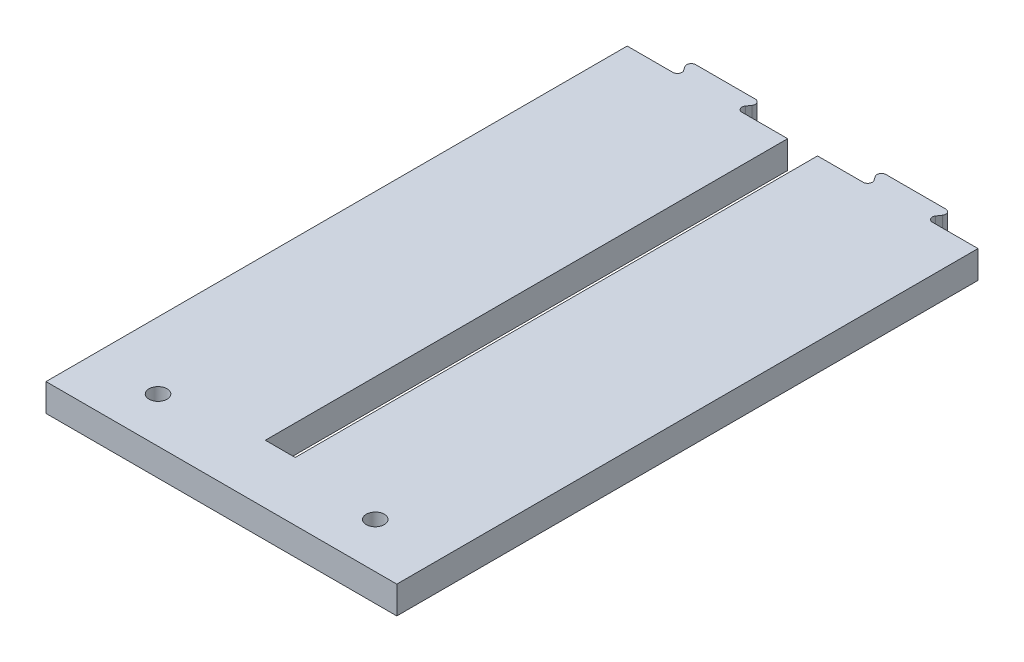
SolidWorks part; units mm, degrees
ref_plane "Front Plane" through (0, 0, 0) normal (0, 0, 1) x (1, 0, 0)
ref_plane "Top Plane" through (0, 0, 0) normal (0, 1, 0) x (1, 0, 0)
ref_plane "Right Plane" through (0, 0, 0) normal (1, 0, 0) x (0, 0, -1)
sketch "Sketch1" plane through (0, 0, 0) normal (0, 1, 0) x (1, 0, 0)
  line L1 (-19.375, 0) -> (19.375, 0)
  line L2 (-19.375, 0) -> (-19.375, 72.5)
  line L3 (-19.375, 72.5) -> (19.375, 72.5)
  line L4 (19.375, 0) -> (19.375, 72.5)
  point P5 (0, 0)
  dimension "D1" = 38.75
  dimension "D2" = 72.5
extrude "Boss-Extrude1" add sketch "Sketch1" along normal blind 3.05 contours L2 | L1 L4 L3 L2 | L4 region at (0, 0, -36.25)
sketch "Sketch4" plane through (0, 3.05, 0) normal (0, 1, 0) x (1, 0, 0)
  line L0 (-19.375, 72.5) -> (19.375, 72.5) construction
  line L2 (-19.375, 0) -> (19.375, 0) construction
  line L3 (1.65, 70.5) -> (-1.65, 70.5)
  line L4 (-1.65, 70.5) -> (-1.65, 69.5)
  line L5 (-1.65, 69.5) -> (1.65, 69.5)
  line L6 (1.65, 69.5) -> (1.65, 70.5)
  line L7 (0, 0) -> (0, 72.5) construction
  line L9 (1.65, 68.3) -> (-1.65, 68.3)
  line L10 (-1.65, 68.3) -> (-1.65, 6.5)
  line L11 (-1.65, 6.5) -> (1.65, 6.5)
  line L12 (1.65, 6.5) -> (1.65, 68.3)
  point P6 (0, 6.5)
  point P10 (0, 70.5)
  point P22 (0, 68.3)
  dimension "D1" = 2
  dimension "D2" = 1
  dimension "D3" = 1.2
  dimension "D4" = 3.3
  dimension "D7" = 6.5
extrude "Cut-Extrude1" cut sketch "Sketch4" against normal through all contours L5 L7 L3 L4 | L11 L7 L9 L10 | L7 L11 L12 L9 | L7 L5 L6 L3 | L6 L3 L4 L5 region at (0.825, 3.05, -70) region at (0.825, 3.05, -37.4) region at (-0.825, 3.05, -37.4) region at (-0.825, 3.05, -70)
sketch "Sketch7" plane through (0, 3.05, 0) normal (0, 1, 0) x (1, 0, 0)
  line L0 (0, 0) -> (-12, 0)
  line L1 (-19.375, 0) -> (19.375, 0) construction
  line L2 (-12, 0) -> (-12, 5)
  line L4 (0, 0) -> (0, 70) construction
  circle A0 centre (-12, 5) radius 1
  circle A2 centre (12, 5) radius 1
  dimension "D3" = 2
  dimension "D1" = 12
  dimension "D2" = 5
extrude "Cut-Extrude4" cut sketch "Sketch7" against normal through all contours A0 L2 | L2 A0 | A2 region at (-11.3129, 3.05, -4.3129)
sketch "Sketch8" plane through (0, 3.05, 0) normal (0, 1, 0) x (1, 0, 0)
  line L0 (19.375, 0) -> (19.375, 72.5) construction
  line L1 (-19.375, 72.5) -> (19.375, 72.5)
  line L2 (-19.375, 72.5) -> (-19.375, 64.2)
  line L3 (-19.375, 64.2) -> (19.375, 64.2)
  line L4 (19.375, 72.5) -> (19.375, 64.2)
  dimension "D1" = 8.3
extrude "Cut-Extrude5" cut sketch "Sketch8" against normal through all
sketch "Sketch9" plane through (0, 3.05, 0) normal (0, 1, 0) x (1, 0, 0)
  line L0 (-19.375, 64.2) -> (19.375, 64.2) construction
  line L1 (-19.375, 64.2) -> (-19.375, 66.2) construction
  line L2 (19.375, 64.2) -> (19.375, 66.2) construction
  line L3 (-19.375, 66.2) -> (19.375, 66.2) construction
  line L4 (-19.375, 64.2) -> (-13.375, 64.2)
  line L5 (-13.375, 64.2) -> (-14.7625, 66.2)
  line L6 (-14.7625, 66.2) -> (-6.2625, 66.2)
  line L7 (-6.2625, 66.2) -> (-7.65, 64.2)
  line L8 (-7.65, 64.2) -> (-1.65, 64.2)
  line L9 (1.65, 64.2) -> (7.65, 64.2)
  line L10 (7.65, 64.2) -> (6.2625, 66.2)
  line L11 (6.2625, 66.2) -> (14.7625, 66.2)
  line L12 (14.7625, 66.2) -> (13.375, 64.2)
  line L13 (13.375, 64.2) -> (19.375, 64.2)
  line L14 (-13.375, 64.2) -> (-7.65, 64.2)
  line L15 (7.65, 64.2) -> (13.375, 64.2)
  line L16 (-19.375, 66.2) -> (-14.7625, 66.2)
  line L17 (14.7625, 66.2) -> (19.375, 66.2)
  line M1 (-1.65, 64.2) -> (-19.375, 64.2)
  line M5 (19.375, 64.2) -> (1.65, 64.2)
  dimension "D1" = 2
  dimension "D3" = 8.5
  dimension "D4" = 6
extrude "Boss-Extrude3" add sketch "Sketch9" against normal blind 3.05 contours L7 L6 L5 M1 | L12 L11 L10 M5 region at (-10.5125, 3.05, -65.265) region at (10.5125, 3.05, -65.265)
fillet "Fillet2" radius 0.5 8 edges at (13.375, 1.525, -64.2) (-7.65, 1.525, -64.2) (14.7625, 1.525, -66.2) (7.65, 1.525, -64.2) (6.2625, 1.525, -66.2) (-6.2625, 1.525, -66.2) (-14.7625, 1.525, -66.2) (-13.375, 1.525, -64.2)
